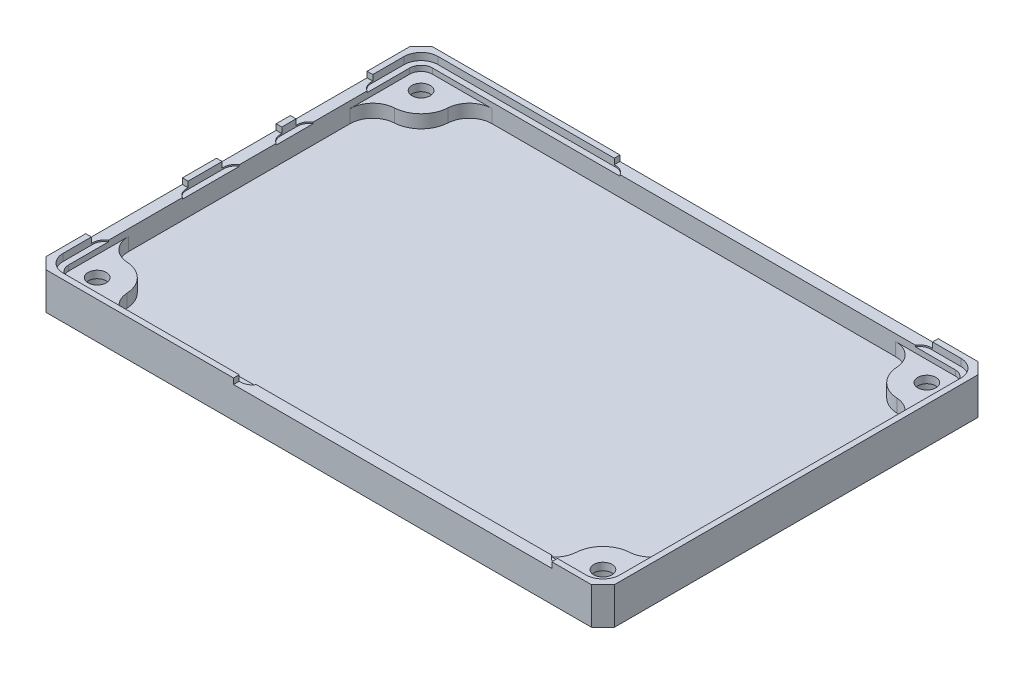
SolidWorks part; units mm, degrees
ref_plane "Front Plane" through (0, 0, 0) normal (0, 0, 1) x (1, 0, 0)
ref_plane "Top Plane" through (0, 0, 0) normal (0, 1, 0) x (1, 0, 0)
ref_plane "Right Plane" through (0, 0, 0) normal (1, 0, 0) x (0, 0, -1)
sketch "Sketch1" plane through (0, 0, 0) normal (0, 1, 0) x (1, 0, 0)
  line L0 (-105.3563, -14.3722) -> (-103.3563, -12.3722)
  line L1 (-103.3563, -12.3722) -> (-7.3563, -12.3722)
  line L2 (-105.3563, -14.3722) -> (-105.3563, -78.3722)
  line L3 (-103.3563, -80.3722) -> (-7.3563, -80.3722)
  line L4 (-5.3563, -14.3722) -> (-5.3563, -78.3722)
  line L5 (-105.3563, -78.3722) -> (-103.3563, -80.3722)
  line L6 (-7.3563, -80.3722) -> (-5.3563, -78.3722)
  line L7 (-7.3563, -12.3722) -> (-5.3563, -14.3722)
  point P0 (-105.3563, -12.3722)
  point P1 (-5.3563, -80.3722)
  point P2 (-105.3563, -80.3722)
  point P3 (-5.3563, -12.3722)
  dimension "D1" = 100
  dimension "D2" = 68
extrude "Boss-Extrude1" add sketch "Sketch1" along normal blind 5.5
sketch "Sketch2" plane through (0, 5.5, 0) normal (0, 1, 0) x (1, 0, 0)
  line L0 (-105.3563, -14.3722) -> (-105.3563, -78.3722) construction
  line L1 (-101.3563, -14.3722) -> (-9.3563, -14.3722)
  line L2 (-103.3563, -16.3722) -> (-103.3563, -76.3722)
  line L3 (-101.3563, -78.3722) -> (-9.3563, -78.3722)
  line L4 (-7.3563, -16.3722) -> (-7.3563, -76.3722)
  line L5 (-7.3563, -12.3722) -> (-103.3563, -12.3722) construction
  line L6 (-103.3563, -80.3722) -> (-7.3563, -80.3722) construction
  line L7 (-5.3563, -78.3722) -> (-5.3563, -14.3722) construction
  arc A0 (-7.3563, -16.3722) -> (-9.3563, -14.3722) centre (-9.3563, -16.3722) ccw
  arc A1 (-103.3563, -16.3722) -> (-101.3563, -14.3722) centre (-101.3563, -16.3722) cw
  arc A2 (-101.3563, -78.3722) -> (-103.3563, -76.3722) centre (-101.3563, -76.3722) cw
  arc A3 (-9.3563, -78.3722) -> (-7.3563, -76.3722) centre (-9.3563, -76.3722) ccw
  point P0 (-103.3563, -14.3722)
  point P1 (-7.3563, -78.3722)
  point P2 (-103.3563, -78.3722)
  point P3 (-7.3563, -14.3722)
  dimension "D5" = 2
  dimension "D6" = 2
  dimension "D7" = 2
  dimension "D8" = 2
  dimension "D1" = 2
  dimension "D2" = 2
  dimension "D3" = 2
  dimension "D4" = 2
extrude "pcb basin" cut sketch "Sketch2" against normal offset from surface (3.5 mm away) 2 up to face at (-55.3563, 0, 46.3722)
sketch "Sketch3" plane through (0, 2, 0) normal (0, 1, 0) x (1, 0, 0)
  line L0 (-103.3563, -80.3722) -> (-7.3563, -80.3722) construction
  line L1 (-55.3563, -12.3722) -> (-55.3563, -80.3722) construction
  line L2 (-103.3563, -69.8722) -> (-99.8563, -69.8722)
  line L4 (-105.3563, -14.3722) -> (-105.3563, -78.3722) construction
  line L5 (-101.3563, -78.3722) -> (-9.3563, -78.3722) construction
  line L6 (-94.8563, -74.8722) -> (-94.8563, -78.3722)
  line L7 (-7.3563, -12.3722) -> (-103.3563, -12.3722) construction
  line L8 (-105.3563, -46.3722) -> (-5.3563, -46.3722) construction
  line L9 (-105.3563, -14.3722) -> (-105.3563, -78.3722) construction
  line L10 (-5.3563, -78.3722) -> (-5.3563, -14.3722) construction
  line L11 (-7.3563, -69.8722) -> (-7.3563, -76.3722)
  line L12 (-101.3563, -78.3722) -> (-94.8563, -78.3722)
  line L13 (-103.3563, -69.8722) -> (-103.3563, -76.3722)
  line L14 (-9.3563, -78.3722) -> (-15.8563, -78.3722)
  line L15 (-15.8563, -74.8722) -> (-15.8563, -78.3722)
  line L16 (-7.3563, -69.8722) -> (-10.8563, -69.8722)
  line L17 (-7.3563, -22.8722) -> (-10.8563, -22.8722)
  line L18 (-15.8563, -17.8722) -> (-15.8563, -14.3722)
  line L19 (-9.3563, -14.3722) -> (-15.8563, -14.3722)
  line L20 (-103.3563, -22.8722) -> (-103.3563, -16.3722)
  line L21 (-101.3563, -14.3722) -> (-94.8563, -14.3722)
  line L22 (-7.3563, -22.8722) -> (-7.3563, -16.3722)
  line L23 (-94.8563, -17.8722) -> (-94.8563, -14.3722)
  line L24 (-103.3563, -16.3722) -> (-103.3563, -76.3722) construction
  line L25 (-103.3563, -22.8722) -> (-99.8563, -22.8722)
  line L27 (-101.3563, -78.3722) -> (-9.3563, -78.3722) construction
  arc A0 (-103.3563, -76.3722) -> (-101.3563, -78.3722) centre (-101.3563, -76.3722) ccw construction
  arc A1 (-103.3563, -76.3722) -> (-101.3563, -78.3722) centre (-101.3563, -76.3722) ccw
  arc A2 (-10.8563, -69.8722) -> (-15.8563, -74.8722) centre (-10.8563, -74.8722) ccw
  arc A3 (-7.3563, -76.3722) -> (-9.3563, -78.3722) centre (-9.3563, -76.3722) cw
  arc A4 (-99.8563, -69.8722) -> (-94.8563, -74.8722) centre (-99.8563, -74.8722) cw
  arc A5 (-99.8563, -22.8722) -> (-94.8563, -17.8722) centre (-99.8563, -17.8722) ccw
  arc A6 (-7.3563, -16.3722) -> (-9.3563, -14.3722) centre (-9.3563, -16.3722) ccw
  arc A7 (-10.8563, -22.8722) -> (-15.8563, -17.8722) centre (-10.8563, -17.8722) cw
  arc A8 (-103.3563, -16.3722) -> (-101.3563, -14.3722) centre (-101.3563, -16.3722) cw
  dimension "D8" = 5
  dimension "D6" = 10.5
  dimension "D7" = 10.5
extrude "pcb posts" add sketch "Sketch3" along normal offset from surface (2.3 mm away) 1.2 up to face at (-55.3563, 5.5, 46.3722)
sketch "Sketch4" plane through (0, 0, 0) normal (0, -1, 0) x (1, 0, 0)
  line L0 (-7.3563, 12.3722) -> (-103.3563, 12.3722) construction
  line L1 (-105.3563, 14.3722) -> (-105.3563, 78.3722) construction
  circle A0 centre (-99.8563, 17.8722) radius 1.6
  circle A1 centre (-10.8563, 17.8722) radius 1.6
  circle A2 centre (-10.8563, 74.8722) radius 1.6
  circle A3 centre (-99.8563, 74.8722) radius 1.6
  dimension "D1" = 3.2
  dimension "D4" = 5.5
  dimension "D5" = 5.5
  dimension "D2" = 2
  dimension "D3" = 2
extrude "screw holes" cut sketch "Sketch4" against normal through all
sketch "Sketch6" plane through (0, 0, 0) normal (0, -1, 0) x (1, 0, 0)
  line L0 (-7.3563, 12.3722) -> (-103.3563, 12.3722) construction
  line L1 (-105.3563, 14.3722) -> (-105.3563, 78.3722) construction
  circle A0 centre (-99.8563, 17.8722) radius 3
  circle A1 centre (-10.8563, 17.8722) radius 3
  circle A2 centre (-10.8563, 74.8722) radius 3
  circle A3 centre (-99.8563, 74.8722) radius 3
  dimension "D1" = 6
  dimension "D4" = 5.5
  dimension "D5" = 5.5
  dimension "D2" = 2
  dimension "D3" = 2
extrude "screw chamfer" cut sketch "Sketch6" against normal blind 3
sketch "Sketch11" plane through (0, 5.5, 0) normal (0, 1, 0) x (1, 0, 0)
  line L8 (-7.3563, -12.3722) -> (-103.3563, -12.3722)
  line L9 (-103.3563, -12.3722) -> (-105.3563, -14.3722)
  line L10 (-105.3563, -14.3722) -> (-105.3563, -78.3722)
  line L11 (-105.3563, -78.3722) -> (-103.3563, -80.3722)
  line L12 (-103.3563, -80.3722) -> (-7.3563, -80.3722)
  line L13 (-7.3563, -80.3722) -> (-5.3563, -78.3722)
  line L14 (-5.3563, -78.3722) -> (-5.3563, -14.3722)
  line L15 (-5.3563, -14.3722) -> (-7.3563, -12.3722)
  line L16 (-7.3563, -12.3722) -> (-103.3563, -12.3722)
  line L17 (-103.3563, -12.3722) -> (-105.3563, -14.3722)
  line L18 (-105.3563, -14.3722) -> (-105.3563, -78.3722)
  line L19 (-105.3563, -78.3722) -> (-103.3563, -80.3722)
  line L20 (-103.3563, -80.3722) -> (-7.3563, -80.3722)
  line L21 (-7.3563, -80.3722) -> (-5.3563, -78.3722)
  line L22 (-5.3563, -78.3722) -> (-5.3563, -14.3722)
  line L23 (-5.3563, -14.3722) -> (-7.3563, -12.3722)
  line L128 (-7.7705, -13.3722) -> (-102.9421, -13.3722)
  line L129 (-102.9421, -13.3722) -> (-104.3563, -14.7864)
  line L130 (-104.3563, -14.7864) -> (-104.3563, -77.958)
  line L131 (-104.3563, -77.958) -> (-102.9421, -79.3722)
  line L132 (-102.9421, -79.3722) -> (-7.7705, -79.3722)
  line L133 (-7.7705, -79.3722) -> (-6.3563, -77.958)
  line L134 (-6.3563, -77.958) -> (-6.3563, -14.7864)
  line L135 (-6.3563, -14.7864) -> (-7.7705, -13.3722)
  line L136 (-9.3563, -13.3722) -> (-101.3563, -13.3722)
  line L138 (-104.3563, -16.3722) -> (-104.3563, -76.3722)
  line L140 (-101.3563, -79.3722) -> (-9.3563, -79.3722)
  line L142 (-6.3563, -76.3722) -> (-6.3563, -16.3722)
  arc A0 (-101.3563, -79.3722) -> (-104.3563, -76.3722) centre (-101.3563, -76.3722) cw
  arc A1 (-104.3563, -16.3722) -> (-101.3563, -13.3722) centre (-101.3563, -16.3722) cw
  arc A2 (-9.3563, -79.3722) -> (-6.3563, -76.3722) centre (-9.3563, -76.3722) ccw
  arc A3 (-6.3563, -16.3722) -> (-9.3563, -13.3722) centre (-9.3563, -16.3722) ccw
  dimension "D3" = 3
  dimension "D4" = 3
  dimension "D5" = 3
  dimension "D6" = 3
  dimension "D1" = 0
  dimension "D2" = 1
extrude "lip" add sketch "Sketch11" along normal blind 1
fillet "basin filit" radius 4 8 edges at (-94.8563, 3.15, 78.3722) (-103.3563, 3.15, 69.8722) (-15.8563, 3.15, 78.3722) (-7.3563, 3.15, 69.8722) (-15.8563, 3.15, 14.3722) (-7.3563, 3.15, 22.8722) (-94.8563, 3.15, 14.3722) (-103.3563, 3.15, 22.8722)
sketch "Sketch12" plane through (-105.3563, 0, 0) normal (-1, 0, 0) x (0, 0, 1)
  line L1 (22.3722, 5.5) -> (34.8722, 5.5) construction
  line L2 (35.3722, 5.5) -> (21.8722, 5.5)
  line L3 (35.3722, 5.5) -> (35.3722, 6.75)
  line L4 (35.3722, 6.75) -> (21.8722, 6.75)
  line L8 (38.3722, 5.5) -> (47.8722, 5.5) construction
  line L9 (37.8722, 5.5) -> (48.3722, 5.5)
  line L10 (37.8722, 5.5) -> (37.8722, 6.75)
  line L11 (37.8722, 6.75) -> (48.3722, 6.75)
  line L12 (48.3722, 5.5) -> (48.3722, 6.75)
  line L13 (78.3722, 6.75) -> (71.3722, 6.75) construction
  line L14 (38.3722, 16.5) -> (38.3722, 5.5) construction
  line L15 (47.8722, 16.5) -> (47.8722, 5.5) construction
  line L16 (21.8722, 5.5) -> (21.8722, 6.75)
  line L17 (22.3722, 16.5) -> (22.3722, 5.5) construction
  line L18 (34.8722, 16.5) -> (34.8722, 5.5) construction
  line L19 (54.8722, 18.5) -> (54.8722, 5.5) construction
  line L20 (71.3722, 6.75) -> (54.3722, 6.75)
  line L21 (71.3722, 6.75) -> (71.3722, 5.5)
  line L22 (71.3722, 5.5) -> (54.3722, 5.5)
  line L23 (54.3722, 6.75) -> (54.3722, 5.5)
  line L24 (70.8722, 18.5) -> (70.8722, 5.5) construction
  dimension "D1" = 0.5
  dimension "D2" = 0.5
  dimension "D3" = 0.5
  dimension "D4" = 0.5
  dimension "D5" = 0.5
  dimension "D6" = 0.5
extrude "interface connector cutout" cut sketch "Sketch12" against normal blind 10
sketch "Sketch13" plane through (0, 0, 12.3722) normal (0, 0, -1) x (-1, 0, 0)
  line L0 (7.3563, 6.5) -> (103.3563, 6.5) construction
  line L1 (14.3563, 6.5) -> (70.3563, 6.5)
  line L2 (14.3563, 6.5) -> (14.3563, 5.5)
  line L3 (14.3563, 5.5) -> (70.3563, 5.5)
  line L4 (70.3563, 6.5) -> (70.3563, 5.5)
  line L5 (63.8563, 5.5) -> (69.8563, 5.5) construction
  line L6 (69.8563, 10.25) -> (69.8563, 5.5) construction
  line L7 (14.8563, 10.25) -> (14.8563, 5.5) construction
  dimension "D1" = 0.5
  dimension "D2" = 0.5
extrude "pop connector cutout" cut sketch "Sketch13" against normal through all
sketch "Sketch14" plane through (0, 5.5, 0) normal (0, 1, 0) x (1, 0, 0)
  line L0 (-103.3563, -37.8722) -> (-103.3563, -39.8722)
  line L1 (-103.3563, -26.8583) -> (-103.3563, -16.3722) construction
  line L3 (-103.3563, -26.8583) -> (-103.3563, -65.8861) construction
  line L5 (-103.3563, -35.3722) -> (-103.3563, -37.8722)
  line L9 (-9.3563, -14.3722) -> (-101.3563, -14.3722)
  line L10 (-7.3563, -76.3722) -> (-7.3563, -16.3722)
  line L11 (-101.3563, -78.3722) -> (-9.3563, -78.3722)
  line L12 (-103.3563, -16.3722) -> (-103.3563, -76.3722)
  line L13 (-9.3563, -14.3722) -> (-14.3563, -14.3722)
  line L14 (-7.3563, -76.3722) -> (-7.3563, -16.3722)
  line L15 (-101.3563, -78.3722) -> (-70.3563, -78.3722)
  line L16 (-103.3563, -16.3722) -> (-103.3563, -21.8722)
  line L21 (-103.3563, -48.3722) -> (-103.3563, -54.3722)
  line L22 (-103.3563, -71.3722) -> (-103.3563, -76.3722)
  line L23 (-14.3563, -78.3722) -> (-9.3563, -78.3722)
  line L24 (-101.3563, -79.3722) -> (-70.3563, -79.3722)
  line L25 (-70.3563, -79.3722) -> (-70.3563, -80.3722)
  line L26 (-70.3563, -80.3722) -> (-14.3563, -80.3722)
  line L27 (-14.3563, -80.3722) -> (-14.3563, -79.3722)
  line L28 (-14.3563, -79.3722) -> (-9.3563, -79.3722)
  line L29 (-6.3563, -76.3722) -> (-6.3563, -16.3722)
  line L30 (-9.3563, -13.3722) -> (-14.3563, -13.3722)
  line L31 (-14.3563, -13.3722) -> (-14.3563, -12.3722)
  line L32 (-14.3563, -12.3722) -> (-70.3563, -12.3722)
  line L33 (-70.3563, -12.3722) -> (-70.3563, -13.3722)
  line L34 (-70.3563, -13.3722) -> (-101.3563, -13.3722)
  line L35 (-104.3563, -16.3722) -> (-104.3563, -21.8722)
  line L36 (-104.3563, -21.8722) -> (-105.3563, -21.8722)
  line L37 (-105.3563, -21.8722) -> (-105.3563, -35.3722)
  line L38 (-105.3563, -35.3722) -> (-104.3563, -35.3722)
  line L39 (-104.3563, -35.3722) -> (-104.3563, -37.8722)
  line L40 (-104.3563, -37.8722) -> (-105.3563, -37.8722)
  line L41 (-105.3563, -37.8722) -> (-105.3563, -48.3722)
  line L42 (-105.3563, -48.3722) -> (-104.3563, -48.3722)
  line L43 (-104.3563, -48.3722) -> (-104.3563, -54.3722)
  line L44 (-104.3563, -54.3722) -> (-105.3563, -54.3722)
  line L45 (-105.3563, -54.3722) -> (-105.3563, -71.3722)
  line L46 (-105.3563, -71.3722) -> (-104.3563, -71.3722)
  line L47 (-104.3563, -71.3722) -> (-104.3563, -76.3722)
  line L48 (-101.3563, -79.3722) -> (-70.3563, -79.3722)
  line L49 (-70.3563, -14.3722) -> (-101.3563, -14.3722)
  line L51 (-103.3563, -16.3722) -> (-103.3563, -76.3722) construction
  line L52 (-14.3563, -79.3722) -> (-9.3563, -79.3722)
  line L53 (-6.3563, -76.3722) -> (-6.3563, -16.3722)
  line L54 (-9.3563, -13.3722) -> (-14.3563, -13.3722)
  line L56 (-104.3563, -21.8722) -> (-104.3563, -23.8722)
  line L57 (-104.3563, -23.8722) -> (-103.3563, -23.8722)
  line L58 (-70.3563, -13.3722) -> (-101.3563, -13.3722)
  line L59 (-104.3563, -16.3722) -> (-104.3563, -21.8722)
  line L60 (-103.3563, -21.8722) -> (-103.3563, -23.8722)
  line L62 (-104.3563, -35.3722) -> (-104.3563, -33.3722)
  line L63 (-104.3563, -35.3722) -> (-104.3563, -37.8722)
  line L64 (-104.3563, -33.3722) -> (-103.3563, -33.3722)
  line L65 (-103.3563, -35.3722) -> (-103.3563, -33.3722)
  line L67 (-104.3563, -48.3722) -> (-104.3563, -54.3722)
  line L68 (-104.3563, -37.8722) -> (-104.3563, -39.8722)
  line L69 (-104.3563, -39.8722) -> (-103.3563, -39.8722)
  line L71 (-104.3563, -71.3722) -> (-104.3563, -76.3722)
  line L73 (-104.3563, -48.3722) -> (-104.3563, -46.3722)
  line L74 (-104.3563, -46.3722) -> (-103.3563, -46.3722)
  line L75 (-103.3563, -48.3722) -> (-103.3563, -46.3722)
  line L77 (-103.3563, -71.3722) -> (-103.3563, -69.3722)
  line L78 (-103.3563, -69.3722) -> (-104.3563, -69.3722)
  line L79 (-104.3563, -71.3722) -> (-104.3563, -69.3722)
  line L81 (-104.3563, -54.3722) -> (-104.3563, -56.3722)
  line L82 (-104.3563, -56.3722) -> (-103.3563, -56.3722)
  line L83 (-103.3563, -54.3722) -> (-103.3563, -56.3722)
  line L84 (-9.3563, -78.3722) -> (-19.8424, -78.3722) construction
  line L85 (-70.3563, -78.3722) -> (-68.3563, -78.3722)
  line L87 (-70.3563, -79.3722) -> (-68.3563, -79.3722)
  line L88 (-68.3563, -78.3722) -> (-68.3563, -79.3722)
  line L89 (-14.3563, -79.3722) -> (-16.3563, -79.3722)
  line L91 (-14.3563, -78.3722) -> (-16.3563, -78.3722)
  line L92 (-16.3563, -79.3722) -> (-16.3563, -78.3722)
  line L93 (-19.8424, -14.3722) -> (-9.3563, -14.3722) construction
  line L94 (-14.3563, -13.3722) -> (-16.3563, -13.3722)
  line L96 (-14.3563, -14.3722) -> (-16.3563, -14.3722)
  line L97 (-16.3563, -13.3722) -> (-16.3563, -14.3722)
  line L98 (-19.8424, -14.3722) -> (-90.8702, -14.3722) construction
  line L99 (-70.3563, -13.3722) -> (-68.3563, -13.3722)
  line L101 (-70.3563, -14.3722) -> (-68.3563, -14.3722)
  line L102 (-68.3563, -13.3722) -> (-68.3563, -14.3722)
  arc A4 (-9.3563, -79.3722) -> (-6.3563, -76.3722) centre (-9.3563, -76.3722) ccw
  arc A5 (-6.3563, -16.3722) -> (-9.3563, -13.3722) centre (-9.3563, -16.3722) ccw
  arc A6 (-101.3563, -13.3722) -> (-104.3563, -16.3722) centre (-101.3563, -16.3722) ccw
  arc A7 (-104.3563, -76.3722) -> (-101.3563, -79.3722) centre (-101.3563, -76.3722) ccw
  arc A8 (-9.3563, -79.3722) -> (-6.3563, -76.3722) centre (-9.3563, -76.3722) ccw
  arc A9 (-6.3563, -16.3722) -> (-9.3563, -13.3722) centre (-9.3563, -16.3722) ccw
  arc A10 (-101.3563, -13.3722) -> (-104.3563, -16.3722) centre (-101.3563, -16.3722) ccw
  arc A11 (-104.3563, -76.3722) -> (-101.3563, -79.3722) centre (-101.3563, -76.3722) ccw
  arc A14 (-101.3563, -14.3722) -> (-103.3563, -16.3722) centre (-101.3563, -16.3722) ccw
  arc A15 (-7.3563, -16.3722) -> (-9.3563, -14.3722) centre (-9.3563, -16.3722) ccw
  arc A16 (-9.3563, -78.3722) -> (-7.3563, -76.3722) centre (-9.3563, -76.3722) ccw
  arc A17 (-103.3563, -76.3722) -> (-101.3563, -78.3722) centre (-101.3563, -76.3722) ccw
  arc A18 (-101.3563, -14.3722) -> (-103.3563, -16.3722) centre (-101.3563, -16.3722) ccw
  arc A19 (-7.3563, -16.3722) -> (-9.3563, -14.3722) centre (-9.3563, -16.3722) ccw
  arc A20 (-9.3563, -78.3722) -> (-7.3563, -76.3722) centre (-9.3563, -76.3722) ccw
  arc A21 (-103.3563, -76.3722) -> (-101.3563, -78.3722) centre (-101.3563, -76.3722) ccw
  dimension "D3" = 2
  dimension "D4" = 2
  dimension "D5" = 2
  dimension "D6" = 2
  dimension "D7" = 2
  dimension "D8" = 2
  dimension "D9" = 2
  dimension "D10" = 2
  dimension "D11" = 2
  dimension "D1" = 0
  dimension "D2" = 0
extrude "Cut-Extrude3" cut sketch "Sketch14" against normal blind 0.25
fillet "Fillet7" radius 2 10 edges at (-68.3563, 5.375, 79.3722) (-16.3563, 5.375, 79.3722) (-16.3563, 5.375, 13.3722) (-104.3563, 5.375, 23.8722) (-68.3563, 5.375, 13.3722) (-104.3563, 5.375, 69.3722) (-104.3563, 5.375, 46.3722) (-104.3563, 5.375, 56.3722) (-104.3563, 5.375, 39.8722) (-104.3563, 5.375, 33.3722)
